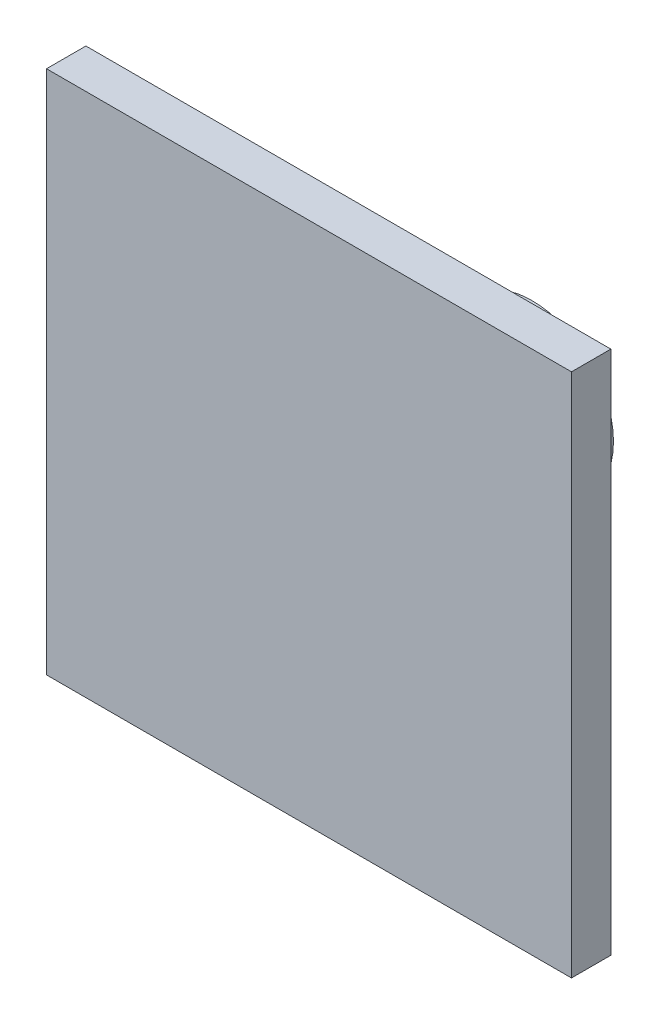
SolidWorks part; units mm, degrees
material "Сосна"
ref_plane "Front" through (0, 0, 0) normal (0, 0, 1) x (1, 0, 0)
ref_plane "Top" through (0, 0, 0) normal (0, 1, 0) x (1, 0, 0)
ref_plane "Right" through (0, 0, 0) normal (1, 0, 0) x (0, 0, -1)
sketch "Эскиз2" plane through (0, 0, 0) normal (0, 0, 1) x (1, 0, 0)
  line L1 (-10, -10) -> (10, -10)
  line L2 (-10, -10) -> (-10, 10)
  line L3 (-10, 10) -> (10, 10)
  line L4 (10, -10) -> (10, 10)
  line L5 (-10, -10) -> (10, 10) construction
  line L6 (-10, 10) -> (10, -10) construction
  point P0 (0, 0)
  dimension "D1" = 20
extrude "Основание" add sketch "Эскиз2" along normal blind 1.5
sketch "Эскиз3" plane through (0, 0, 0) normal (0, 0, 1) x (1, 0, 0)
  circle A0 centre (0, 0) radius 1.1
  circle A1 centre (0, 0) radius 3.1
  dimension "D1" = 2.2
  dimension "D2" = 2
  dimension "D3" = 6.2
extrude "Стойка" add sketch "Эскиз3" against normal blind 7
chamfer "Фаска1" distance 2 angle 45 1 edges at (3.1, 0, 0)
